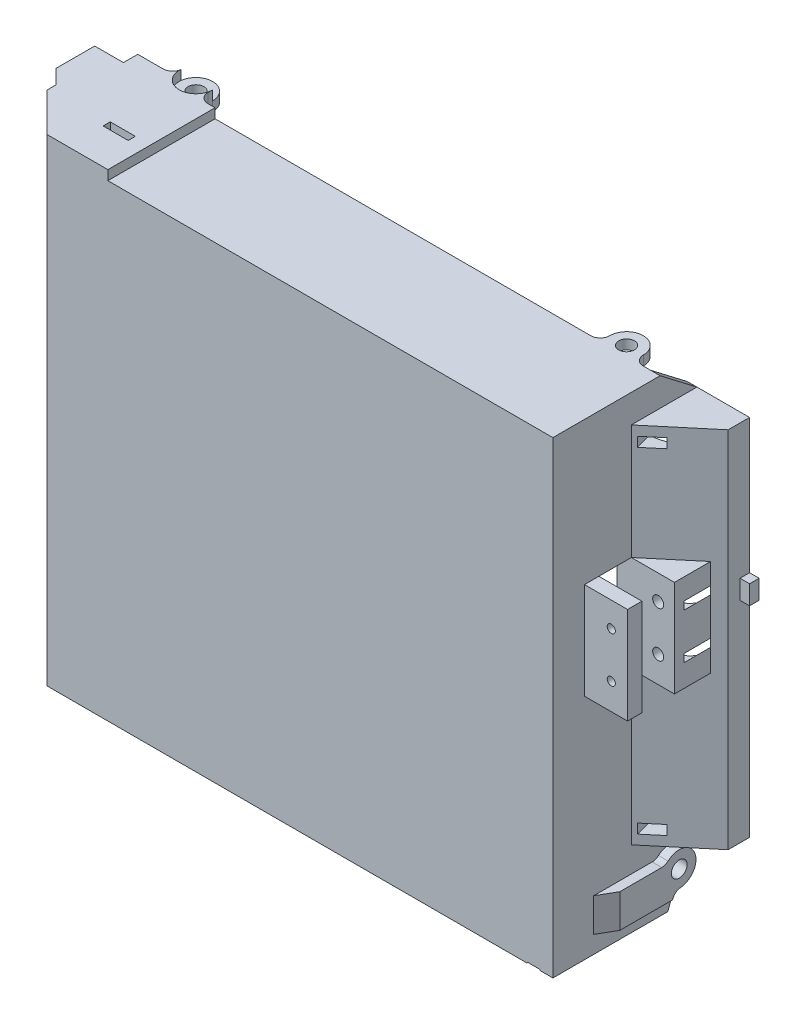
SolidWorks part; units mm, degrees
ref_plane "前视基准面" through (0, 0, 0) normal (0, 0, 1) x (1, 0, 0)
ref_plane "上视基准面" through (0, 0, 0) normal (0, 1, 0) x (1, 0, 0)
ref_plane "右视基准面" through (0, 0, 0) normal (1, 0, 0) x (0, 0, -1)
other "Configuration Table"
sketch "草图1" plane through (0, 0, 0) normal (0, 1, 0) x (1, 0, 0)
  line L1 (0, 0) -> (114.75, 0)
  line L2 (0, 0) -> (0, 22)
  line L3 (0, 22) -> (114.75, 22)
  line L4 (114.75, 0) -> (114.75, 22)
  line L5 (0, 0) -> (114.75, 22) construction
  line L6 (0, 22) -> (114.75, 0) construction
  point P4 (57.375, 11)
  dimension "D1" = 114.75
  dimension "D2" = 22
extrude "凸台-拉伸1" add sketch "草图1" along normal blind 2
sketch "草图2" plane through (0, 2, 0) normal (0, 1, 0) x (1, 0, 0)
  line L0 (16.75, 23.4) -> (16.75, 22) construction
  line L1 (114.75, 22) -> (0, 22) construction
  line L2 (0, 22) -> (0, 0) construction
  line L3 (0, 0) -> (114.75, 0) construction
  line L4 (20.25, 23.4) -> (20.25, 22)
  line L5 (13.25, 23.4) -> (13.25, 22)
  line L6 (107.75, 22) -> (107.75, 22.4) construction
  line L7 (104.25, 22) -> (104.25, 22.4)
  line L8 (111.25, 22) -> (111.25, 22.4)
  circle A0 centre (16.75, 23.4) radius 1.65
  arc A1 (20.25, 23.4) -> (13.25, 23.4) centre (16.75, 23.4) ccw
  arc A2 (13.25, 22) -> (20.25, 22) centre (16.75, 22) ccw
  arc A3 (104.25, 22) -> (111.25, 22) centre (107.75, 22) ccw
  arc A4 (111.25, 22.4) -> (104.25, 22.4) centre (107.75, 22.4) ccw
  circle A5 centre (107.75, 22.4) radius 1.65
  point P6 (16.75, 22.7)
  point P16 (107.75, 22.2)
  dimension "D1" = 16.75
  dimension "D2" = 3.3
  dimension "D3" = 23.4
  dimension "D4" = 3.5
  dimension "D5" = 1
  dimension "D7" = 3.5
  dimension "D6" = 91
extrude "凸台-拉伸2" add sketch "草图2" against normal up to surface (2 mm away) up to face at (57.375, 0, -11)
sketch "草图3" plane through (0, 2, 0) normal (0, 1, 0) x (1, 0, 0)
  circle A0 centre (16.75, 23.4) radius 1.65
  circle A1 centre (107.75, 22.4) radius 1.65
extrude "切除-拉伸1" cut sketch "草图3" against normal blind 10
sketch "草图4" plane through (0, 0, 0) normal (0, -1, 0) x (1, 0, 0)
  line L0 (0, -22) -> (0, 0) construction
  line L1 (114.75, 0) -> (21.75, 0)
  line L2 (114.75, 0) -> (114.75, -17)
  line L3 (114.75, -17) -> (21.75, -17)
  line L4 (21.75, 0) -> (21.75, -17)
  line L5 (114.75, 0) -> (21.75, -17) construction
  line L6 (114.75, -17) -> (21.75, 0) construction
  point P4 (68.25, -8.5)
  dimension "D1" = 21.75
  dimension "D2" = 17
extrude "凸台-拉伸3" add sketch "草图4" along normal blind 1
sketch "草图5" plane through (0, 0, 0) normal (0, -1, 0) x (1, 0, 0)
  line L1 (0, -22) -> (6, -22)
  line L2 (0, -22) -> (0, -19)
  line L3 (0, -19) -> (6, -19)
  line L4 (6, -22) -> (6, -19)
  line L5 (0, -22) -> (6, -19) construction
  line L6 (0, -19) -> (6, -22) construction
  point P4 (3, -20.5)
  dimension "D1" = 3
  dimension "D2" = 6
extrude "切除-拉伸2" cut sketch "草图5" against normal up to next
sketch "草图6" plane through (0, 0, 0) normal (0, -1, 0) x (1, 0, 0)
  line L0 (0, 0) -> (21.75, 0) construction
  line L1 (14.15, -5.4) -> (19.4, -5.4)
  line L2 (14.15, -5.4) -> (14.15, -6.9)
  line L3 (14.15, -6.9) -> (19.4, -6.9)
  line L4 (19.4, -5.4) -> (19.4, -6.9)
  line L5 (14.15, -5.4) -> (19.4, -6.9) construction
  line L6 (14.15, -6.9) -> (19.4, -5.4) construction
  line L7 (0, -19) -> (0, 0) construction
  point P4 (16.775, -6.15)
  dimension "D1" = 6.9
  dimension "D2" = 1.5
  dimension "D3" = 14.15
  dimension "D4" = 5.25
extrude "切除-拉伸3" cut sketch "草图6" against normal up to next
sketch "草图7" plane through (0, 0, 0) normal (0, -1, 0) x (1, 0, 0)
  line L0 (14.15, -6.9) -> (19.4, -6.9) construction
  line L1 (21.75, 0) -> (16.75, 0)
  line L2 (21.75, 0) -> (21.75, -17)
  line L3 (21.75, -17) -> (16.75, -17)
  line L4 (16.75, 0) -> (16.75, -5.4)
  line L5 (21.75, 0) -> (16.75, -17) construction
  line L6 (21.75, -17) -> (16.75, 0) construction
  line L7 (19.4, -6.9) -> (19.4, -5.4) construction
  line L8 (19.4, -5.4) -> (14.15, -5.4) construction
  line L9 (16.75, -6.9) -> (19.4, -6.9)
  line L10 (19.4, -6.9) -> (19.4, -5.4)
  line L11 (19.4, -5.4) -> (16.75, -5.4)
  line L12 (16.75, -6.9) -> (16.75, -17)
  point P4 (19.25, -8.5)
  dimension "D1" = 5
extrude "凸台-拉伸4" add sketch "草图7" along normal blind 0.5
sketch "草图8" plane through (0, 0, 0) normal (0, -1, 0) x (1, 0, 0)
  line L1 (0, 0) -> (3, 0)
  line L2 (0, 0) -> (0, -10.9)
  line L3 (0, -10.9) -> (3, -10.9)
  line L4 (3, 0) -> (3, -10.9)
  line L5 (0, 0) -> (3, -10.9) construction
  line L6 (0, -10.9) -> (3, 0) construction
  line L7 (6, -19) -> (0, -19) construction
  point P4 (1.5, -5.45)
  dimension "D1" = 8.1
  dimension "D2" = 3
extrude "切除-拉伸4" cut sketch "草图8" against normal up to next
chamfer "倒角1" distance 3 angle 45 1 edges at (3, 1, -10.9)
chamfer "倒角2" distance 6 angle 45 1 edges at (3, 1, 0)
sketch "草图9" plane through (114.75, 0, 0) normal (1, 0, 0) x (0, 0, -1)
  line L1 (0, 2) -> (22, 2)
  line L2 (0, 2) -> (0, -95.8)
  line L3 (0, -95.8) -> (22, -95.8)
  line L4 (22, 2) -> (22, -95.8)
  line L5 (0, 2) -> (22, -95.8) construction
  line L6 (0, -95.8) -> (22, 2) construction
  point P4 (11, -46.9)
  dimension "D1" = 97.8
extrude "凸台-拉伸5" add sketch "草图9" along normal blind 2
sketch "草图10" plane through (0, 0, -17) normal (0, 0, -1) x (-1, 0, 0)
  line L1 (-114.75, 0) -> (-113.75, 0)
  line L2 (-114.75, 0) -> (-114.75, -95.8)
  line L3 (-114.75, -95.8) -> (-113.75, -95.8)
  line L4 (-113.75, 0) -> (-113.75, -95.8)
  line L5 (-114.75, 0) -> (-113.75, -95.8) construction
  line L6 (-114.75, -95.8) -> (-113.75, 0) construction
  point P4 (-114.25, -47.9)
  dimension "D1" = 1
extrude "凸台-拉伸6" add sketch "草图10" against normal up to surface (17 mm away) up to face at (55.8, -19.06, 0)
fillet "圆角2" radius 3 1 edges at (114.75, 0, -19.5)
sketch "草图11" plane through (0, -95.8, 0) normal (0, -1, 0) x (1, 0, 0)
  line L0 (116.75, -22) -> (114.75, -22) construction
  line L1 (115.35, -22) -> (113.75, -22)
  line L2 (115.35, -22) -> (115.35, 0)
  line L3 (115.35, 0) -> (113.75, 0)
  line L4 (113.75, -22) -> (113.75, 0)
  line L5 (115.35, -22) -> (113.75, 0) construction
  line L6 (115.35, 0) -> (113.75, -22) construction
  line L7 (116.75, 0) -> (116.75, -22) construction
  point P4 (114.55, -11)
  dimension "D1" = 1.4
extrude "切除-拉伸6" cut sketch "草图11" against normal blind 1.6
sketch "草图12" plane through (113.75, 0, 0) normal (-1, 0, 0) x (0, 0, 1)
  line L1 (-19, -90.175) -> (-12, -90.175)
  line L2 (-19, -90.175) -> (-19, -87.175)
  line L3 (-19, -87.175) -> (-12, -87.175)
  line L4 (-12, -90.175) -> (-12, -87.175)
  line L5 (-19, -90.175) -> (-12, -87.175) construction
  line L6 (-19, -87.175) -> (-12, -90.175) construction
  line L7 (-22, -95.8) -> (0, -95.8) construction
  line L8 (-22, -94.2) -> (-22, -3) construction
  point P4 (-15.5, -88.675)
  dimension "D1" = 7.125
  dimension "D2" = 3
  dimension "D3" = 3
  dimension "D4" = 7
extrude "切除-拉伸7" cut sketch "草图12" against normal up to next
sketch "草图13" plane through (116.75, 0, 0) normal (1, 0, 0) x (0, 0, -1)
  line L0 (22, -95.8) -> (22, 2) construction
  line L1 (0, -95.8) -> (22, -95.8) construction
  line L2 (19, -87.175) -> (19, -90.175) construction
  line L3 (12, -87.175) -> (19, -87.175) construction
  line L4 (19, -87.175) -> (19, -88.1057)
  line L5 (18.9014, -87.175) -> (19, -87.175)
  circle A0 centre (22.4, -87.275) radius 1.65
  arc A1 (19, -88.1057) -> (18.9014, -87.175) centre (22.4, -87.275) ccw
  dimension "D1" = 3.3
  dimension "D2" = 0.4
  dimension "D3" = 7
  dimension "D4" = 8.525
extrude "凸台-拉伸7" add sketch "草图13" against normal up to surface (2 mm away) up to face at (114.75, -68.6375, -18.75)
sketch "草图14" plane through (116.75, 0, 0) normal (1, 0, 0) x (0, 0, -1)
  line L0 (12, -87.175) -> (19, -87.175) construction
  line L1 (21, -85.175) -> (10, -85.175)
  line L2 (21, -85.175) -> (21, -92.175)
  line L3 (21, -92.175) -> (10, -92.175)
  line L4 (10, -85.175) -> (10, -92.175)
  line L5 (21, -85.175) -> (10, -92.175) construction
  line L6 (21, -92.175) -> (10, -85.175) construction
  line L7 (19, -90.175) -> (12, -90.175) construction
  line L8 (12, -90.175) -> (12, -87.175) construction
  line L9 (19, -87.175) -> (19, -90.175) construction
  point P4 (15.5, -88.675)
  dimension "D1" = 2
  dimension "D2" = 2
  dimension "D3" = 2
  dimension "D4" = 2
extrude "凸台-拉伸8" add sketch "草图14" along normal blind 2
chamfer "倒角3" distance 2 angle 60 1 edges at (116.75, -88.675, -10) first distance on face at (117.75, -88.675, -10)
sketch "草图15" plane through (116.75, 0, 0) normal (1, 0, 0) x (0, 0, -1)
  circle A0 centre (22.4, -87.275) radius 1.65
  circle A1 centre (22.4, -87.275) radius 3.5
extrude "凸台-拉伸9" add sketch "草图15" along normal up to surface (2 mm away) up to face at (118.75, -88.675, -15.5)
sketch "草图16" plane through (118.75, 0, 0) normal (1, 0, 0) x (0, 0, -1)
  circle A0 centre (22.4, -87.275) radius 1.65
  arc A1 (21, -88.1482) -> (21, -86.4018) centre (22.4, -87.275) ccw construction
extrude "切除-拉伸8" cut sketch "草图16" against normal up to next
sketch "草图17" plane through (0, 0, -22) normal (0, 0, -1) x (-1, 0, 0)
  line L4 (-20.25, 2) -> (-104.25, 2)
  line L5 (-104.25, 2) -> (-104.25, 0)
  line L6 (-116.75, 2) -> (-116.75, -83.7979)
  line L7 (-116.75, -83.7979) -> (-114.75, -83.7979)
  line L8 (-114.75, -83.7979) -> (-114.75, -3)
  line L9 (-111.75, 0) -> (-111.25, 0)
  line L10 (-111.25, 0) -> (-111.25, 2)
  line L11 (-111.25, 2) -> (-116.75, 2)
  line L12 (-116.75, 2) -> (-116.75, -83.7979)
  line L13 (-116.75, -83.7979) -> (-114.75, -83.7979)
  line L14 (-114.75, -83.7979) -> (-114.75, -3)
  line L15 (-111.75, 0) -> (-111.25, 0)
  line L16 (-111.25, 0) -> (-111.25, 2)
  line L17 (-111.25, 2) -> (-116.75, 2)
  line L18 (-104.25, 0) -> (-20.25, 0)
  line L19 (-20.25, 0) -> (-20.25, 2)
  line L20 (-20.25, 2) -> (-104.25, 2)
  line L21 (-104.25, 2) -> (-104.25, 0)
  line L22 (-104.25, 0) -> (-20.25, 0)
  line L23 (-20.25, 0) -> (-20.25, 2)
  arc A1 (-111.75, 0) -> (-114.75, -3) centre (-111.75, -3) ccw
  arc A2 (-111.75, 0) -> (-114.75, -3) centre (-111.75, -3) ccw
  dimension "D1" = 0
  dimension "D2" = 0
extrude "切除-拉伸9" cut sketch "草图17" against normal blind 1.6
fillet "圆角3" radius 2 2 edges at (115.75, -90.7521, -22) (115.75, -83.7979, -20.4)
fillet "圆角4" radius 2 6 edges at (117.75, -85.175, -19.6) (117.75, -90.4828, -21) (20.25, 1, -20.4) (13.25, 1, -22) (104.25, 1, -20.4) (111.25, 1, -20.4)
sketch "草图18" plane through (0, 0, 0) normal (0, 0, 1) x (1, 0, 0)
  line L1 (9, 2) -> (116.75, 2)
  line L2 (9, 2) -> (9, -95.8)
  line L3 (9, -95.8) -> (116.75, -95.8)
  line L4 (116.75, 2) -> (116.75, -95.8)
  line L5 (9, 2) -> (116.75, -95.8) construction
  line L6 (9, -95.8) -> (116.75, 2) construction
  point P4 (62.875, -46.9)
extrude "凸台-拉伸10" add sketch "草图18" along normal blind 2
sketch "草图19" plane through (0, 2, 0) normal (0, 1, 0) x (1, 0, 0)
  line L0 (9, 0) -> (11, -2)
  line L1 (116.75, -2) -> (9, -2) construction
  line L2 (11, -2) -> (9, -2)
  line L3 (9, -2) -> (9, 0)
extrude "切除-拉伸10" cut sketch "草图19" against normal up to next
sketch "草图20" plane through (0, -94.2, 0) normal (0, -1, 0) x (1, 0, 0)
  line L0 (11, 2) -> (116.75, 2) construction
  line L1 (116.75, 2) -> (116.75, -22) construction
  circle A0 centre (112.75, -1.5) radius 1.25
  circle A1 centre (112.75, -1.5) radius 3.3
  dimension "D1" = 3.5
  dimension "D2" = 4
  dimension "D3" = 6.6
  dimension "D4" = 2.5
extrude "凸台-拉伸11" add sketch "草图20" against normal blind 5 from offset 1.5 offset against normal yes
sketch "草图21" plane through (0, -94.2, 0) normal (0, -1, 0) x (1, 0, 0)
  circle A0 centre (112.75, -1.5) radius 1.25
  arc A1 (113.75, -0.75) -> (113.75, -2.25) centre (112.75, -1.5) ccw construction
extrude "切除-拉伸11" cut sketch "草图21" against normal up to surface (6.5 mm away) up to face at (112.2027, -87.7, -1.7914)
fillet "圆角5" radius 1 2 edges at (113.75, -90.2, -4.6448) (109.8106, -90.2, 0)
sketch "草图23" plane through (0, -92.7, 0) normal (0, -1, 0) x (1, 0, 0)
  line L0 (113.75, -17) -> (114.75, -17) construction
  line L1 (113.75, 0) -> (114.45, 0)
  line L2 (113.75, 0) -> (113.75, -17)
  line L3 (113.75, -17) -> (114.45, -17)
  line L4 (114.45, 0) -> (114.45, -17)
  line L5 (113.75, 0) -> (114.45, -17) construction
  line L6 (113.75, -17) -> (114.45, 0) construction
  line L7 (116.75, 2) -> (116.75, -22) construction
  point P4 (114.1, -8.5)
  dimension "D1" = 2.3
extrude "切除-拉伸12" cut sketch "草图23" along normal up to surface (3.1 mm away) up to face at (80.7, -95.8, -6.6667)
sketch "草图24" plane through (0, -95.8, 0) normal (0, -1, 0) x (1, 0, 0)
  circle A0 centre (112.75, -1.5) radius 3.75
  dimension "D1" = 7.5
extrude "切除-拉伸14" cut sketch "草图24" against normal blind 0.2
sketch "草图25" plane through (0, -94.2, 0) normal (0, -1, 0) x (1, 0, 0)
  line L0 (115.35, 0) -> (115.35, -4.2023) construction
  line L1 (114.45, 0) -> (115.35, 0)
  line L2 (114.45, 0) -> (114.45, -3.7)
  line L3 (114.45, -3.7) -> (115.35, -3.7)
  line L4 (115.35, 0) -> (115.35, -3.7)
  line L5 (114.45, 0) -> (115.35, -3.7) construction
  line L6 (114.45, -3.7) -> (115.35, 0) construction
  circle A0 centre (112.75, -1.5) radius 1.25 construction
  point P4 (114.9, -1.85)
  dimension "D1" = 2.2
extrude "切除-拉伸15" cut sketch "草图25" against normal up to surface (1.5 mm away) up to face at (112.75, -92.7, -2.75)
fillet "圆角6" radius 1 1 edges at (114.45, -93.45, -3.7)
sketch "草图26" plane through (116.75, 0, 0) normal (1, 0, 0) x (0, 0, -1)
  line L0 (-2, -95.8) -> (-2, 2) construction
  line L1 (-2, -95.8) -> (22, -95.8) construction
  circle A0 centre (1.25, -71.8) radius 1.1
  circle A1 centre (1.25, -71.8) radius 3.25 construction
  dimension "D1" = 2.2
  dimension "D2" = 6.5
  dimension "D3" = 24
sketch "草图32" plane through (116.75, 0, 0) normal (1, 0, 0) x (0, 0, -1)
  line L0 (20.4, 2) -> (-2, 2) construction
  line L1 (7.6, -27.9) -> (14.4, -27.9)
  line L2 (7.6, -27.9) -> (7.6, -48.1)
  line L3 (7.6, -48.1) -> (14.4, -48.1)
  line L4 (14.4, -27.9) -> (14.4, -48.1)
  line L5 (7.6, -27.9) -> (14.4, -48.1) construction
  line L6 (7.6, -48.1) -> (14.4, -27.9) construction
  line L7 (-2, -95.8) -> (-2, 2) construction
  point P4 (11, -38)
  dimension "D1" = 6.8
  dimension "D2" = 20.2
  dimension "D3" = 40
  dimension "D4" = 13
extrude "切除-拉伸19" cut sketch "草图32" against normal up to next
sketch "草图33" plane through (116.75, 0, 0) normal (1, 0, 0) x (0, 0, -1)
  line L1 (7.6, -27.9) -> (4.6, -27.9)
  line L2 (7.6, -27.9) -> (7.6, -48.1)
  line L3 (7.6, -48.1) -> (4.6, -48.1)
  line L4 (4.6, -27.9) -> (4.6, -48.1)
  line L5 (7.6, -27.9) -> (4.6, -48.1) construction
  line L6 (7.6, -48.1) -> (4.6, -27.9) construction
  line L7 (14.4, -27.9) -> (16.4, -27.9)
  line L8 (14.4, -27.9) -> (14.4, -48.1)
  line L9 (14.4, -48.1) -> (16.4, -48.1)
  line L10 (16.4, -27.9) -> (16.4, -48.1)
  line L11 (14.4, -27.9) -> (16.4, -48.1) construction
  line L12 (14.4, -48.1) -> (16.4, -27.9) construction
  point P4 (6.1, -38)
  point P12 (15.4, -38)
  dimension "D1" = 3
  dimension "D2" = 2
extrude "凸台-拉伸12" add sketch "草图33" along normal blind 9
sketch "草图34" plane through (0, 0, -7.6) normal (0, 0, -1) x (-1, 0, 0)
  line L0 (-125.75, -27.9) -> (-116.75, -27.9) construction
  line L1 (-125.75, -48.1) -> (-125.75, -27.9) construction
  line L2 (-122.35, -33.1) -> (-122.35, -42.6) construction
  circle A0 centre (-122.35, -33.1) radius 0.85
  circle A1 centre (-122.35, -42.6) radius 0.85
  dimension "D1" = 1.7
  dimension "D2" = 5.2
  dimension "D3" = 3.4
  dimension "D4" = 9.5
extrude "切除-拉伸20" cut sketch "草图34" against normal up to next
sketch "草图35" plane through (0, 0, -14.4) normal (0, 0, 1) x (1, 0, 0)
  circle A0 centre (122.35, -33.1) radius 1.15
  circle A1 centre (122.35, -42.6) radius 1.15
  circle A2 centre (122.35, -33.1) radius 0.85 construction
  dimension "D1" = 2.3
extrude "切除-拉伸21" cut sketch "草图35" against normal up to next
sketch "草图36" plane through (0, -27.9, 0) normal (0, 1, 0) x (1, 0, 0)
  line L0 (121.05, 16.4) -> (116.75, 20.4)
  line L1 (125.75, 16.4) -> (116.75, 16.4) construction
  line L2 (116.75, 20.4) -> (116.75, 16.4)
  line L3 (116.75, 16.4) -> (121.05, 16.4)
  dimension "D1" = 4.3
extrude "凸台-拉伸13" add sketch "草图36" against normal up to surface (20.2 mm away) up to face at (121.25, -48.1, -15.4)
sketch "草图37" plane through (64.334, 0, -69.1591) normal (0.6811, 0, -0.7322) x (-0.7322, 0, -0.6811)
  line L4 (-77.4611, -48.1) -> (-71.5883, -48.1)
  line L5 (-71.5883, -48.1) -> (-71.5883, -27.9)
  line L6 (-71.5883, -27.9) -> (-77.4611, -27.9)
  line L7 (-77.4611, -27.9) -> (-77.4611, -48.1)
  line L8 (-77.4611, -48.1) -> (-71.5883, -48.1)
  line L9 (-71.5883, -48.1) -> (-71.5883, -27.9)
  line L10 (-71.5883, -27.9) -> (-77.4611, -27.9)
  line L11 (-77.4611, -27.9) -> (-77.4611, -48.1)
  dimension "D1" = 0
extrude "凸台-拉伸14" add sketch "草图37" along normal blind 0.19
sketch "草图38" plane through (0, 0, -20.4) normal (0, 0, -1) x (-1, 0, 0)
  line L0 (-114.75, -81.8383) -> (-114.75, -3) construction
  line L1 (-116.8794, -27.9) -> (-114.75, -27.9)
  line L2 (-116.8794, -27.9) -> (-116.8794, -48.1)
  line L3 (-116.8794, -48.1) -> (-114.75, -48.1)
  line L4 (-114.75, -27.9) -> (-114.75, -48.1)
  line L5 (-116.8794, -27.9) -> (-114.75, -48.1) construction
  line L6 (-116.8794, -48.1) -> (-114.75, -27.9) construction
  point P4 (-115.8147, -38)
sketch "草图39" plane through (56.716, 0, 52.7591) normal (0.7322, 0, 0.6811) x (0.6811, 0, -0.7322)
  line L4 (94.4555, -27.9) -> (94.4555, -48.1)
  line L5 (94.4555, -48.1) -> (94.6455, -48.1)
  line L6 (94.6455, -48.1) -> (94.6455, -27.9)
  line L7 (94.6455, -27.9) -> (94.4555, -27.9)
  line L8 (94.4555, -27.9) -> (94.4555, -48.1)
  line L9 (94.4555, -48.1) -> (94.6455, -48.1)
  line L10 (94.6455, -48.1) -> (94.6455, -27.9)
  line L11 (94.6455, -27.9) -> (94.4555, -27.9)
  dimension "D1" = 0
extrude "凸台-拉伸17" add sketch "草图39" along normal up to surface (0.2042 mm away) up to face at (122.35, -34.25, -16.4)
sketch "草图40" plane through (0, 0, -16.4) normal (0, 0, -1) x (-1, 0, 0)
  circle A0 centre (-122.35, -33.1) radius 3.5
  circle A1 centre (-122.35, -42.6) radius 3.5
  dimension "D1" = 7
extrude "切除-拉伸22" cut sketch "草图40" along normal up to next
sketch "草图41" plane through (0, -27.9, 0) normal (0, 1, 0) x (1, 0, 0)
  line L0 (116.75, 20.4) -> (117.029, 20.4)
  line L1 (116.8794, 20.5391) -> (121.329, 16.4) construction
  line L2 (117.029, 20.4) -> (116.8794, 20.5391)
  line L3 (116.8794, 20.5391) -> (116.75, 20.4)
extrude "切除-拉伸23" cut sketch "草图41" against normal up to next
sketch "草图42" plane through (0, -27.9, 0) normal (0, 1, 0) x (1, 0, 0)
  line L0 (121.829, 16.4) -> (124.6197, 19.4)
  line L1 (125.75, 16.4) -> (121.329, 16.4) construction
  line L2 (124.6197, 19.4) -> (125.75, 19.4)
  line L3 (125.75, 19.4) -> (125.75, 16.4)
  line L4 (125.75, 16.4) -> (121.829, 16.4)
  line L5 (117.029, 20.4) -> (121.329, 16.4) construction
  dimension "D1" = 0.5
  dimension "D2" = 3
extrude "凸台-拉伸18" add sketch "草图42" against normal up to surface (20.2 mm away) up to face at (120.5597, -48.1, -17.0667)
sketch "草图43" plane through (0, 0, -16.4) normal (0, 0, -1) x (-1, 0, 0)
  circle A0 centre (-122.35, -33.1) radius 3.5
  circle A1 centre (-122.35, -42.6) radius 3.5
extrude "切除-拉伸24" cut sketch "草图43" along normal up to next
sketch "草图44" plane through (0, -27.9, 0) normal (0, 1, 0) x (1, 0, 0)
  line L0 (116.75, 20.4) -> (116.75, -2) construction
  line L1 (116.75, 20.4) -> (114.75, 20.4) construction
  circle A0 centre (116.05, 27.9) radius 9.5
  dimension "D1" = 19
  dimension "D2" = 0.7
  dimension "D3" = 7.5
extrude "切除-拉伸25" cut sketch "草图44" along normal blind 22 and the other way blind 50
sketch "草图45" plane through (0, -27.9, 0) normal (0, 1, 0) x (1, 0, 0)
  line L2 (121.829, 16.4) -> (121.329, 16.4)
  line L3 (121.329, 16.4) -> (118.7559, 18.7935)
  line L4 (125.75, 14.4) -> (116.75, 14.4) construction
  line L9 (121.829, 16.4) -> (124.6197, 19.4)
  line L10 (125.2152, 25.4) -> (125.75, 25.4)
  line L11 (125.75, 25.4) -> (125.75, 19.4)
  line L12 (124.6197, 19.4) -> (125.75, 19.4)
  arc A0 (118.7559, 18.7935) -> (125.2152, 25.4) centre (116.05, 27.9) ccw
  arc A1 (114.75, 18.4894) -> (116.75, 18.4258) centre (116.05, 27.9) ccw construction
  dimension "D1" = 11
extrude "凸台-拉伸19" add sketch "草图45" against normal up to surface (20.2 mm away) up to face at (121.4429, -48.1, -17.1957)
sketch "草图46" plane through (0, 0, -16.4) normal (0, 0, -1) x (-1, 0, 0)
  circle A0 centre (-122.35, -33.1) radius 3.5
  circle A1 centre (-122.35, -42.6) radius 3.5
  arc A4 (-121.829, -39.139) -> (-125.75, -41.7693) centre (-122.35, -42.6) ccw construction
  arc A5 (-121.829, -29.639) -> (-125.75, -32.2693) centre (-122.35, -33.1) ccw construction
extrude "切除-拉伸26" cut sketch "草图46" along normal up to next
sketch "草图47" plane through (0, -48.1, 0) normal (0, -1, 0) x (1, 0, 0)
  line L0 (116.75, -14.4) -> (125.75, -21.9519)
  line L1 (125.75, -14.4) -> (125.75, -25.4) construction
  line L2 (125.75, -21.9519) -> (125.75, -25.4)
  line L3 (125.75, -25.4) -> (125.2152, -25.4)
  line L4 (116.75, -14.4) -> (116.75, -18.4258)
  line L5 (125.75, -14.4) -> (116.75, -14.4) construction
  arc A0 (125.2152, -25.4) -> (116.75, -18.4258) centre (116.05, -27.9) ccw construction
  arc A1 (125.2152, -25.4) -> (116.75, -18.4258) centre (116.05, -27.9) ccw
  dimension "D1" = 40
extrude "凸台-拉伸20" add sketch "草图47" along normal offset from surface (31.8 mm away) 2 up to face at (115.7496, -77.9, -19.4156) offset beyond the face yes
sketch "草图50" plane through (0, -27.9, 0) normal (0, 1, 0) x (1, 0, 0)
  line L4 (125.75, 25.4) -> (125.2152, 25.4)
  line L5 (125.75, 21.9519) -> (125.75, 25.4)
  line L6 (116.75, 14.4) -> (125.75, 21.9519)
  line L7 (116.75, 18.4258) -> (116.75, 14.4)
  line L8 (125.75, 25.4) -> (125.2152, 25.4)
  line L9 (125.75, 21.9519) -> (125.75, 25.4)
  line L10 (116.75, 14.4) -> (125.75, 21.9519)
  line L11 (116.75, 18.4258) -> (116.75, 14.4)
  arc A1 (116.75, 18.4258) -> (125.2152, 25.4) centre (116.05, 27.9) ccw
  arc A2 (116.75, 18.4258) -> (125.2152, 25.4) centre (116.05, 27.9) ccw
  dimension "D1" = 0
extrude "凸台-拉伸23" add sketch "草图50" along normal offset from surface (24 mm away) 2 up to face at (115.7496, -5.9, -19.4156) offset beyond the face yes
sketch "草图48" plane through (0, -79.9, 0) normal (0, -1, 0) x (1, 0, 0)
  line L0 (116.75, -27.9) -> (125.75, -27.9)
  line L1 (125.75, -27.9) -> (125.75, -25.4)
  line L4 (125.2152, -25.4) -> (125.75, -25.4)
  line L5 (125.75, -25.4) -> (125.75, -21.9519)
  line L6 (125.75, -21.9519) -> (116.75, -14.4)
  line L7 (116.75, -14.4) -> (116.75, -18.4258)
  line L9 (125.75, -25.4) -> (125.75, -21.9519)
  line L10 (125.75, -21.9519) -> (116.75, -14.4)
  line L11 (116.75, -14.4) -> (116.75, -27.9)
  arc A1 (125.2152, -25.4) -> (116.75, -18.4258) centre (116.05, -27.9) ccw
  arc A3 (125.2152, -25.4) -> (116.75, -18.4258) centre (116.05, -27.9) ccw construction
  point P0 (116.05, -27.9)
  dimension "D1" = 0
extrude "凸台-拉伸21" add sketch "草图48" against normal up to surface (2 mm away) up to face at (115.7496, -77.9, -19.4156)
sketch "草图51" plane through (0, -3.9, 0) normal (0, 1, 0) x (1, 0, 0)
  line L5 (116.75, 20.4) -> (116.75, 14.4)
  line L6 (116.75, 27.9) -> (116.75, 20.4)
  line L7 (125.75, 27.9) -> (116.75, 27.9)
  line L8 (125.75, 21.9519) -> (125.75, 27.9)
  line L9 (116.75, 14.4) -> (125.75, 21.9519)
  line L10 (116.75, 20.4) -> (116.75, 14.4)
  line L11 (116.75, 27.9) -> (116.75, 20.4)
  line L12 (125.75, 27.9) -> (116.75, 27.9)
  line L13 (125.75, 21.9519) -> (125.75, 27.9)
  line L14 (116.75, 14.4) -> (125.75, 21.9519)
  dimension "D1" = 0
extrude "凸台-拉伸25" add sketch "草图51" against normal up to surface (2 mm away) up to face at (115.7496, -5.9, -19.4156)
sketch "草图49" plane through (125.75, 0, 0) normal (1, 0, 0) x (0, 0, -1)
  line L1 (21.9519, -79.9) -> (27.9, -79.9)
  line L2 (21.9519, -79.9) -> (21.9519, -3.9)
  line L3 (21.9519, -3.9) -> (27.9, -3.9)
  line L4 (27.9, -79.9) -> (27.9, -3.9)
  line L5 (21.9519, -79.9) -> (27.9, -3.9) construction
  line L6 (21.9519, -3.9) -> (27.9, -79.9) construction
  line L7 (21.9519, -3.9) -> (21.9519, -27.9) construction
  point P4 (24.9259, -41.9)
extrude "凸台-拉伸22" add sketch "草图49" along normal blind 2
sketch "草图52" plane through (0, 0, -27.9) normal (0, 0, -1) x (-1, 0, 0)
  line L8 (-116.75, -79.9) -> (-116.75, -77.9)
  line L9 (-116.75, -77.9) -> (-125.75, -77.9)
  line L10 (-125.75, -77.9) -> (-125.75, -5.9)
  line L11 (-125.75, -5.9) -> (-116.75, -5.9)
  line L12 (-116.75, -5.9) -> (-116.75, -3.9)
  line L13 (-116.75, -3.9) -> (-127.75, -3.9)
  line L14 (-127.75, -3.9) -> (-127.75, -79.9)
  line L15 (-127.75, -79.9) -> (-116.75, -79.9)
  line L16 (-116.75, -79.9) -> (-116.75, -77.9)
  line L17 (-116.75, -77.9) -> (-125.75, -77.9)
  line L18 (-125.75, -77.9) -> (-125.75, -5.9)
  line L19 (-125.75, -5.9) -> (-116.75, -5.9)
  line L20 (-116.75, -5.9) -> (-116.75, -3.9)
  line L21 (-116.75, -3.9) -> (-127.75, -3.9)
  line L22 (-127.75, -3.9) -> (-127.75, -79.9)
  line L23 (-127.75, -79.9) -> (-116.75, -79.9)
  dimension "D1" = 0
extrude "凸台-拉伸26" add sketch "草图52" along normal blind 0.2
sketch "草图53" plane through (0, 0, -20.4) normal (0, 0, -1) x (-1, 0, 0)
  line L1 (-114.75, -5.9) -> (-116.75, -5.9)
  line L2 (-114.75, -5.9) -> (-114.75, -3.9)
  line L3 (-114.75, -3.9) -> (-116.75, -3.9)
  line L4 (-116.75, -5.9) -> (-116.75, -3.9)
  line L5 (-114.75, -5.9) -> (-116.75, -3.9) construction
  line L6 (-114.75, -3.9) -> (-116.75, -5.9) construction
  line L7 (-116.75, -79.9) -> (-114.75, -79.9)
  line L8 (-116.75, -79.9) -> (-116.75, -77.9)
  line L9 (-116.75, -77.9) -> (-114.75, -77.9)
  line L10 (-114.75, -79.9) -> (-114.75, -77.9)
  line L11 (-116.75, -79.9) -> (-114.75, -77.9) construction
  line L12 (-116.75, -77.9) -> (-114.75, -79.9) construction
  point P4 (-115.75, -4.9)
  point P11 (-115.75, -78.9)
extrude "凸台-拉伸27" add sketch "草图53" along normal up to surface (7.7 mm away) up to face at (121.75, -41.9, -28.1)
sketch "草图54" plane through (0, -77.9, 0) normal (0, 1, 0) x (1, 0, 0)
  line L0 (124.55, 27.9) -> (125.75, 27.9)
  line L1 (125.75, 28.1) -> (125.75, 25.4) construction
  line L2 (125.75, 27.9) -> (125.75, 25.4)
  line L3 (125.75, 25.4) -> (125.2152, 25.4)
  line L4 (114.75, 28.1) -> (114.75, 18.4894) construction
  line L5 (114.75, 19.5) -> (114.75, 18.4894)
  arc A0 (114.75, 19.5) -> (124.55, 27.9) centre (116.05, 27.9) ccw
  arc A1 (114.75, 18.4894) -> (125.2152, 25.4) centre (116.05, 27.9) ccw construction
  arc A2 (114.75, 18.4894) -> (125.2152, 25.4) centre (116.05, 27.9) ccw
  dimension "D1" = 8.5
extrude "凸台-拉伸28" add sketch "草图54" along normal blind 1
sketch "草图55" plane through (0, -77.9, 0) normal (0, 1, 0) x (1, 0, 0)
  line L0 (116.2563, 19.4025) -> (120.12, 20.4378)
  line L1 (120.12, 20.4378) -> (121.305, 16.0154)
  line L2 (121.305, 16.0154) -> (117.4413, 14.9801)
  line L3 (117.4413, 14.9801) -> (116.2563, 19.4025)
  line L4 (116.05, 27.9) -> (119.3732, 15.4977) construction
  line L5 (114.75, 28.1) -> (114.75, 19.5) construction
  line L6 (116.75, 14.4) -> (125.75, 21.9519) construction
  arc A0 (114.75, 19.5) -> (124.55, 27.9) centre (116.05, 27.9) ccw construction
  dimension "D1" = 4
  dimension "D2" = 15
extrude "切除-拉伸27" cut sketch "草图55" along normal blind 2
ref_plane "基准面1" through (0, -41.9, 0) normal (0, -1, 0) x (-1, 0, 0)
mirror "镜向1" about plane through (0, -41.9, 0) normal (0, -1, 0) of "切除-拉伸27", "凸台-拉伸28"
sketch "草图57" plane through (114.75, 0, 0) normal (-1, 0, 0) x (0, 0, 1)
  line L0 (-28.1, -79.9) -> (-25.7086, -86.1334)
  line L1 (-22, -95.8) -> (-22, -94.2)
  line L2 (-22, -94.2) -> (-22, -92.5371)
  line L3 (-28.1, -79.9) -> (-20.4, -79.9) construction
  line L4 (-20.4, -81.8383) -> (-20.4, -79.9) construction
  line L5 (-28.1, -79.9) -> (-20.4, -79.9)
  line L6 (-20.4, -81.8383) -> (-20.4, -79.9)
  line L7 (-24.096, -90.3366) -> (-22, -95.8)
  line L8 (-28.1, -3.9) -> (-20.4, 2)
  line L13 (-20.4, 2) -> (-20.4, -3.9)
  line L14 (-28.1, -3.9) -> (-20.4, -3.9)
  arc A0 (-22, -83.7979) -> (-20.4, -81.8383) centre (-22.4, -81.8383) ccw construction
  arc A1 (-22, -83.7979) -> (-23.4182, -90.6236) centre (-22.4, -87.275) ccw construction
  arc A2 (-22, -92.5371) -> (-23.4182, -90.6236) centre (-24, -92.5371) ccw construction
  arc A3 (-22, -83.7979) -> (-20.4, -81.8383) centre (-22.4, -81.8383) ccw
  arc A4 (-22, -83.7979) -> (-25.7086, -86.1334) centre (-22.4, -87.275) ccw
  arc A5 (-22, -92.5371) -> (-23.4182, -90.6236) centre (-24, -92.5371) ccw
  arc A6 (-24.096, -90.3366) -> (-23.4182, -90.6236) centre (-22.4, -87.275) ccw
extrude "凸台-拉伸30" add sketch "草图57" against normal up to surface (2 mm away) up to face at (116.75, -60.9125, -14.3217)
sketch "草图58" plane through (0, -79.9, 0) normal (0, -1, 0) x (1, 0, 0)
  line L0 (125.75, -21.9519) -> (127.75, -23.6301)
  line L1 (127.75, -21.9519) -> (127.75, -28.1) construction
  line L2 (127.75, -23.6301) -> (127.75, -21.9519)
  line L3 (127.75, -21.9519) -> (125.75, -21.9519)
  line L4 (116.75, -14.4) -> (125.75, -21.9519) construction
extrude "切除-拉伸28" cut sketch "草图58" against normal up to next
sketch "草图59" plane through (127.75, 0, 0) normal (1, 0, 0) x (0, 0, -1)
  line L0 (28.1, -3.9) -> (28.1, -79.9) construction
  line L1 (28.1, -32) -> (26.1, -32)
  line L2 (28.1, -32) -> (28.1, -36)
  line L3 (28.1, -36) -> (26.1, -36)
  line L4 (26.1, -32) -> (26.1, -36)
  line L5 (28.1, -32) -> (26.1, -36) construction
  line L6 (28.1, -36) -> (26.1, -32) construction
  line L8 (28.1, -3.9) -> (14.4, -3.9) construction
  point P4 (27.1, -34)
  dimension "D1" = 2
  dimension "D2" = 30.1
  dimension "D3" = 4
extrude "凸台-拉伸31" add sketch "草图59" along normal blind 2
sketch "草图60" plane through (0, -0.5, 0) normal (0, -1, 0) x (1, 0, 0)
  line L8 (21.75, -17) -> (21.75, 0)
  line L9 (21.75, 0) -> (16.75, 0)
  line L10 (16.75, 0) -> (16.75, -5.4)
  line L11 (16.75, -5.4) -> (19.4, -5.4)
  line L12 (19.4, -5.4) -> (19.4, -6.9)
  line L13 (19.4, -6.9) -> (16.75, -6.9)
  line L14 (16.75, -6.9) -> (16.75, -17)
  line L15 (16.75, -17) -> (21.75, -17)
  line L16 (21.75, -17) -> (21.75, 0)
  line L17 (21.75, 0) -> (16.75, 0)
  line L18 (16.75, 0) -> (16.75, -5.4)
  line L19 (16.75, -5.4) -> (19.4, -5.4)
  line L20 (19.4, -5.4) -> (19.4, -6.9)
  line L21 (19.4, -6.9) -> (16.75, -6.9)
  line L22 (16.75, -6.9) -> (16.75, -17)
  line L23 (16.75, -17) -> (21.75, -17)
  dimension "D1" = 0
extrude "切除-拉伸29" cut sketch "草图60" against normal up to surface (0.5 mm away) up to face at (32.6632, 0, -15.096)
sketch "草图61" plane through (0, 0, 0) normal (0, -1, 0) x (1, 0, 0)
  line L0 (0, -19) -> (0, -10.9) construction
  line L1 (21.75, -17) -> (0, -17)
  line L2 (21.75, -17) -> (21.75, 0)
  line L3 (21.75, 0) -> (0, 0)
  line L4 (0, -17) -> (0, 0)
  line L5 (21.75, -17) -> (0, 0) construction
  line L6 (21.75, 0) -> (0, -17) construction
  point P4 (10.875, -8.5)
  point P6 (21.75, 0)
  point P8 (0, -17)
extrude "切除-拉伸30" cut sketch "草图61" against normal blind 1.5
sketch "草图62" plane through (0, 2, 0) normal (0, 1, 0) x (1, 0, 0)
  line L0 (23.75, 20.4) -> (23.75, -2)
  line L1 (21.75, 0) -> (21.75, 17) construction
  line L13 (3, 6) -> (11, -2)
  line L14 (11, -2) -> (116.75, -2)
  line L15 (116.75, -2) -> (116.75, 20.4)
  line L16 (116.75, 20.4) -> (114.75, 20.4)
  line L17 (114.75, 20.4) -> (113.25, 20.4)
  line L18 (102.25, 20.4) -> (22.25, 20.4)
  line L19 (20.25, 22.4) -> (20.25, 23.4)
  line L20 (11.2828, 22) -> (6, 22)
  line L21 (6, 22) -> (6, 19)
  line L22 (6, 19) -> (0, 19)
  line L23 (0, 19) -> (0, 10.9)
  line L24 (0, 10.9) -> (3, 7.9)
  line L25 (3, 7.9) -> (3, 6)
  line L26 (3, 6) -> (11, -2)
  line L27 (11, -2) -> (23.75, -2)
  line L31 (23.75, 20.4) -> (22.25, 20.4)
  line L32 (20.25, 22.4) -> (20.25, 23.4)
  line L33 (11.2828, 22) -> (6, 22)
  line L34 (6, 22) -> (6, 19)
  line L35 (6, 19) -> (0, 19)
  line L36 (0, 19) -> (0, 10.9)
  line L37 (0, 10.9) -> (3, 7.9)
  line L38 (3, 7.9) -> (3, 6)
  arc A0 (13.2709, 23.7818) -> (20.25, 23.4) centre (16.75, 23.4) ccw
  arc A6 (111.25, 22.4) -> (113.25, 20.4) centre (113.25, 22.4) ccw
  arc A7 (111.25, 22.4) -> (104.25, 22.4) centre (107.75, 22.4) ccw
  arc A8 (102.25, 20.4) -> (104.25, 22.4) centre (102.25, 22.4) ccw
  arc A9 (20.25, 22.4) -> (22.25, 20.4) centre (22.25, 22.4) ccw
  arc A10 (20.25, 23.4) -> (13.2709, 23.7818) centre (16.75, 23.4) ccw
  arc A11 (11.2828, 22) -> (13.2709, 23.7818) centre (11.2828, 24) ccw
  arc A15 (20.25, 22.4) -> (22.25, 20.4) centre (22.25, 22.4) ccw
  arc A17 (11.2828, 22) -> (13.2709, 23.7818) centre (11.2828, 24) ccw
  dimension "D2" = 2
  dimension "D1" = 0
extrude "凸台-拉伸32" add sketch "草图62" along normal blind 2
sketch "草图63" plane through (0, 2, 0) normal (0, -1, 0) x (1, 0, 0)
  line L0 (14.15, -5.4) -> (19.4, -5.4) construction
  line L1 (15.35, -5.4) -> (20.6, -5.4)
  line L2 (15.35, -5.4) -> (15.35, -6.9)
  line L3 (15.35, -6.9) -> (20.6, -6.9)
  line L12 (20.6, -5.4) -> (20.6, -6.9)
  line L13 (15.35, -5.4) -> (20.6, -6.9) construction
  line L14 (15.35, -6.9) -> (20.6, -5.4) construction
  line L15 (19.4, -6.9) -> (14.15, -6.9) construction
  line L16 (19.4, -6.9) -> (14.15, -6.9) construction
  line L17 (14.15, -6.9) -> (14.15, -5.4) construction
  point P4 (17.975, -6.15)
  point P9 (15.4147, -6.9)
  dimension "D1" = 1.2
extrude "切除-拉伸31" cut sketch "草图63" against normal up to next and the other way up to next
